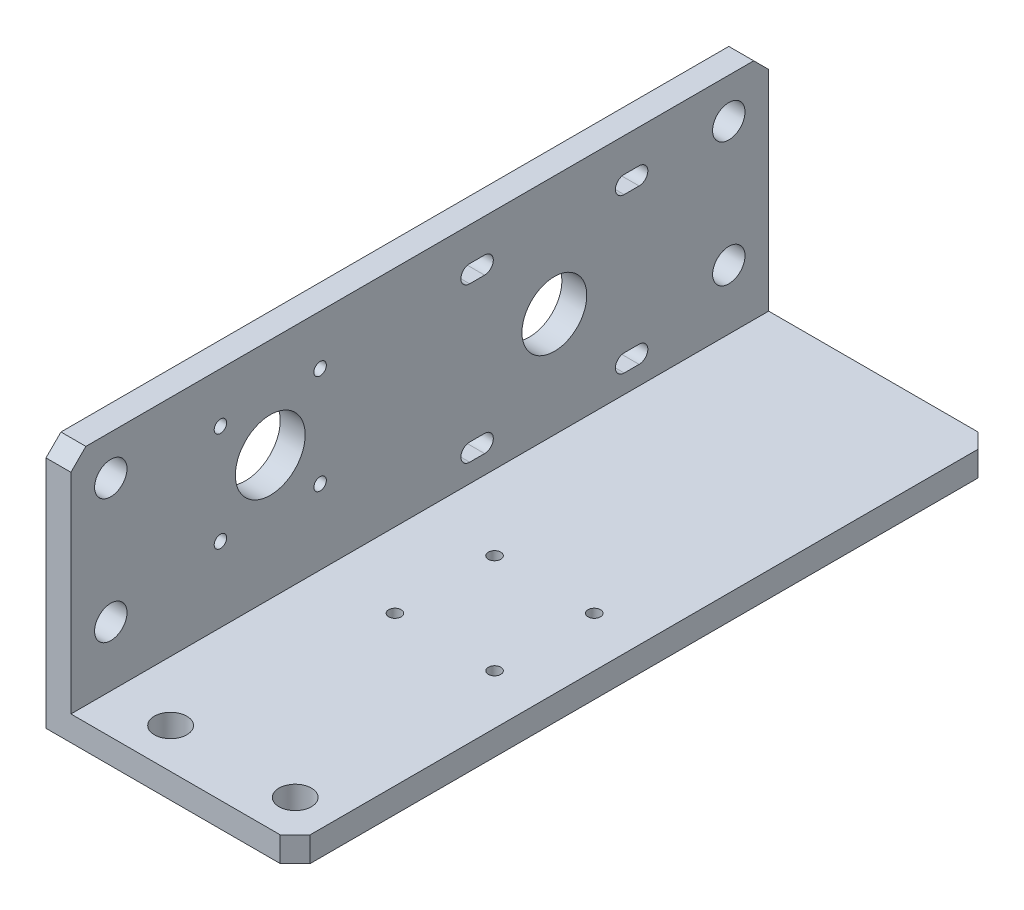
SolidWorks part; units mm, degrees
material "Lega 1060"
ref_plane "Piano frontale" through (0, 0, 0) normal (0, 0, 1) x (1, 0, 0)
ref_plane "Piano superiore" through (0, 0, 0) normal (0, 1, 0) x (1, 0, 0)
ref_plane "Piano destro" through (0, 0, 0) normal (1, 0, 0) x (0, 0, -1)
sketch "Schizzo1" plane through (0, 0, 0) normal (0, 0, 1) x (1, 0, 0)
  line L0 (0, 0) -> (0, 50)
  line L1 (0, 50) -> (5, 50)
  line L2 (5, 50) -> (5, 5)
  line L3 (5, 5) -> (50, 5)
  line L4 (50, 5) -> (50, 0)
  line L5 (50, 0) -> (0, 0)
  dimension "D1" = 5
  dimension "D2" = 5
  dimension "D3" = 50
  dimension "D4" = 50
extrude "Estrusione-Estrusione1" add sketch "Schizzo1" along normal blind 140
sketch "Schizzo2" plane through (0, 0, 0) normal (0, -1, 0) x (1, 0, 0)
  line L0 (5.4524, 132) -> (42.7933, 132) construction
  line L1 (0, 140) -> (50, 140) construction
  line L5 (50, 140) -> (50, 0) construction
  point P4 (17, 132)
  point P5 (42, 132)
  dimension "D1" = 8
  dimension "D2" = 25
  dimension "D3" = 8
sketch "Schizzo3" plane through (0, 0, 0) normal (-1, 0, 0) x (0, 0, 1)
  line L0 (132, 44.621) -> (132, 5.772) construction
  line L1 (140, 50) -> (140, 0) construction
  line L2 (140, 50) -> (0, 50) construction
  point P4 (132, 42)
  point P5 (132, 17)
  dimension "D1" = 8
  dimension "D2" = 8
  dimension "D3" = 25
hole_wizard "Foro Ø6.5 (6.5)-1" positions "Schizzo5" profile "Schizzo4" hole size "Ø6.5" standard "ISO" end condition through all
sketch "Schizzo5" plane through (0, 0, 0) normal (0, -1, 0) x (-1, 0, 0)
  point P0 (-17, -132)
  point P3 (-42, -132)
sketch "Schizzo4" plane through (17, 0, 132) normal (1, 0, 0) x (0, 0, -1)
  line L0 (0, 0) -> (0, 50)
  line L1 (0, 50) -> (3.25, 50)
  line L2 (3.25, 50) -> (3.25, 0)
  line L5 (3.25, 0) -> (0, 0)
  line L11 (0, -6.35) -> (0, 107.95) construction
  dimension "Thru Hole Dia." = 6.5
  dimension "Thru Hole Depth" = 50
hole_wizard "Foro Ø6.5 (6.5)-2" positions "Schizzo7" profile "Schizzo6" hole size "Ø6.5" standard "ISO"
sketch "Schizzo7" plane through (0, 0, 0) normal (-1, 0, 0) x (0, 0, 1)
  point P1 (132, 42)
  point P4 (132, 17)
sketch "Schizzo6" plane through (0, 42, 132) normal (0, 1, 0) x (0, 0, 1)
  line L0 (0, 0) -> (0, 6.9528)
  line L1 (0, 6.9528) -> (3.25, 5)
  line L2 (3.25, 5) -> (3.25, 0)
  line L5 (3.25, 0) -> (0, 0)
  line L10 (0, 6.9528) -> (-3.25, 5) construction
  line L11 (0, -6.35) -> (0, 107.95) construction
  dimension "Hole Dia." = 6.5
  dimension "Hole Depth" = 5
  dimension "Drill Angle" = 118
ref_plane "Piano1" through (0, 0, 70) normal (0, 0, 1) x (1, 0, 0)
mirror "Specchia1" about plane through (0, 0, 70) normal (0, 0, 1) of "Foro Ø6.5 (6.5)-2"
sketch "Schizzo8" plane through (0, 0, 0) normal (0, -1, 0) x (1, 0, 0)
  line L0 (30, 80) -> (7.0316, 80) construction
  line L1 (30, 80) -> (-7.1051, 42.8949) construction
  line L2 (0, 140) -> (50, 140) construction
  line L3 (50, 140) -> (50, 0) construction
  circle A0 centre (20, 70) radius 1.75
  circle A1 centre (20, 90) radius 1.75
  circle A2 centre (40, 90) radius 1.75
  circle A3 centre (40, 70) radius 1.75
  point P18 (30, 80)
  dimension "D3" = 3.5
  dimension "D1" = 60
  dimension "D2" = 20
  dimension "D4" = 45
  dimension "D5" = 20
  dimension "D6" = 4
sketch "Schizzo9" plane through (0, 0, 0) normal (-1, 0, 0) x (0, 0, 1)
  line L2 (140, 50) -> (0, 50) construction
  line L3 (140, 50) -> (140, 0) construction
  circle A4 centre (100, 30) radius 7
  point P18 (100, 30)
  dimension "D7" = 14
  dimension "D1" = 20
  dimension "D2" = 40
extrude "Taglio-Estrusione2" cut sketch "Schizzo9" against normal up to next
sketch "Schizzo11" plane through (0, 0, 0) normal (-1, 0, 0) x (0, 0, 1)
  line L0 (21.0797, 26) -> (64.9203, 26) construction
  line L1 (60, 10.5) -> (57, 10.5) construction
  line L2 (140, 0) -> (0, 0) construction
  line L3 (60, 41.5) -> (57, 41.5) construction
  line L4 (60, 39.75) -> (57, 39.75)
  line L5 (60, 43.25) -> (57, 43.25)
  line L6 (43, 26) -> (43, 48.418) construction
  line L7 (60, 12.25) -> (57, 12.25)
  line L8 (60, 8.75) -> (57, 8.75)
  line L9 (26, 10.5) -> (29, 10.5) construction
  line L10 (26, 12.25) -> (29, 12.25)
  line L11 (26, 8.75) -> (29, 8.75)
  line L12 (26, 41.5) -> (29, 41.5) construction
  line L13 (26, 39.75) -> (29, 39.75)
  line L14 (26, 43.25) -> (29, 43.25)
  circle A0 centre (43, 26) radius 6.5
  arc A1 (60, 39.75) -> (60, 43.25) centre (60, 41.5) ccw
  arc A2 (60, 12.25) -> (60, 8.75) centre (60, 10.5) cw
  arc A3 (57, 8.75) -> (57, 12.25) centre (57, 10.5) cw
  arc A4 (26, 12.25) -> (26, 8.75) centre (26, 10.5) ccw
  arc A5 (29, 8.75) -> (29, 12.25) centre (29, 10.5) ccw
  circle A6 centre (43, 26) radius 21.9203 construction
  arc A7 (57, 43.25) -> (57, 39.75) centre (57, 41.5) ccw
  arc A8 (26, 39.75) -> (26, 43.25) centre (26, 41.5) cw
  arc A9 (29, 43.25) -> (29, 39.75) centre (29, 41.5) cw
  point P10 (58.5, 10.5)
  point P13 (58.5, 41.5)
  point P18 (27.5, 10.5)
  point P20 (43, 26)
  point P33 (27.5, 41.5)
  dimension "D2" = 31
  dimension "D3" = 31
  dimension "D1" = 13
  dimension "D4" = 26
  dimension "D8" = 3.5
  dimension "D9" = 3
extrude "Taglio-Estrusione4" cut sketch "Schizzo11" against normal up to next
chamfer "Smusso1" distance 3 angle 45 4 edges at (50, 2.5, 0) (2.5, 50, 0) (2.5, 50, 140) (50, 2.5, 140)
sketch "Sketch4" plane through (0, 0, 0) normal (-1, 0, 0) x (0, 0, 1)
  line L0 (100, 30) -> (100, 45.3374) construction
  line L1 (100, 30) -> (85.4455, 44.5545) construction
  line L2 (100, 30) -> (85.4455, 30) construction
  point P3 (90, 40)
  point P5 (110, 40)
  point P6 (90, 20)
  point P8 (110, 20)
  dimension "D1" = 45
  dimension "D2" = 10
hole_wizard "M3 Tapped Hole1" positions "3DSketch3" profile "Sketch5" tap size "M3" standard "ISO" end condition through all
sketch3d "3DSketch3"
  point P0 (0, 40, 90)
  point P3 (0, 40, 110)
  point P6 (0, 20, 110)
  point P9 (0, 20, 90)
sketch "Sketch5" plane through (0, 40, 90) normal (0, 1, 0) x (0, 0, 1)
  line L0 (0, 0) -> (0, 50)
  line L1 (0, 50) -> (1.25, 50)
  line L2 (1.25, 50) -> (1.25, 0)
  line L5 (1.25, 0) -> (0, 0)
  line L11 (0, -6.35) -> (0, 107.95) construction
  dimension "Thru Tap Drill Dia." = 2.5
  dimension "Thru Tap Drill Depth" = 50
cosmetic thread "Cosmetic Thread1" parameters "D2"=3
cosmetic thread "Cosmetic Thread2" parameters "D2"=3
cosmetic thread "Cosmetic Thread3" parameters "D2"=3
cosmetic thread "Cosmetic Thread4" parameters "D2"=3
hole_wizard "M3 Tapped Hole2" positions "3DSketch4" profile "Sketch6" tap size "M3" standard "ISO" end condition through all
sketch3d "3DSketch4"
  point P0 (20, 0, 90)
  point P3 (40, 0, 90)
  point P6 (40, 0, 70)
  point P9 (20, 0, 70)
sketch "Sketch6" plane through (20, 0, 90) normal (1, 0, 0) x (0, 0, -1)
  line L0 (0, 0) -> (0, 50)
  line L1 (0, 50) -> (1.25, 50)
  line L2 (1.25, 50) -> (1.25, 0)
  line L5 (1.25, 0) -> (0, 0)
  line L11 (0, -6.35) -> (0, 107.95) construction
  dimension "Thru Tap Drill Dia." = 2.5
  dimension "Thru Tap Drill Depth" = 50
cosmetic thread "Cosmetic Thread5" parameters "D2"=3
cosmetic thread "Cosmetic Thread6" parameters "D2"=3
cosmetic thread "Cosmetic Thread7" parameters "D2"=3
cosmetic thread "Cosmetic Thread8" parameters "D2"=3
